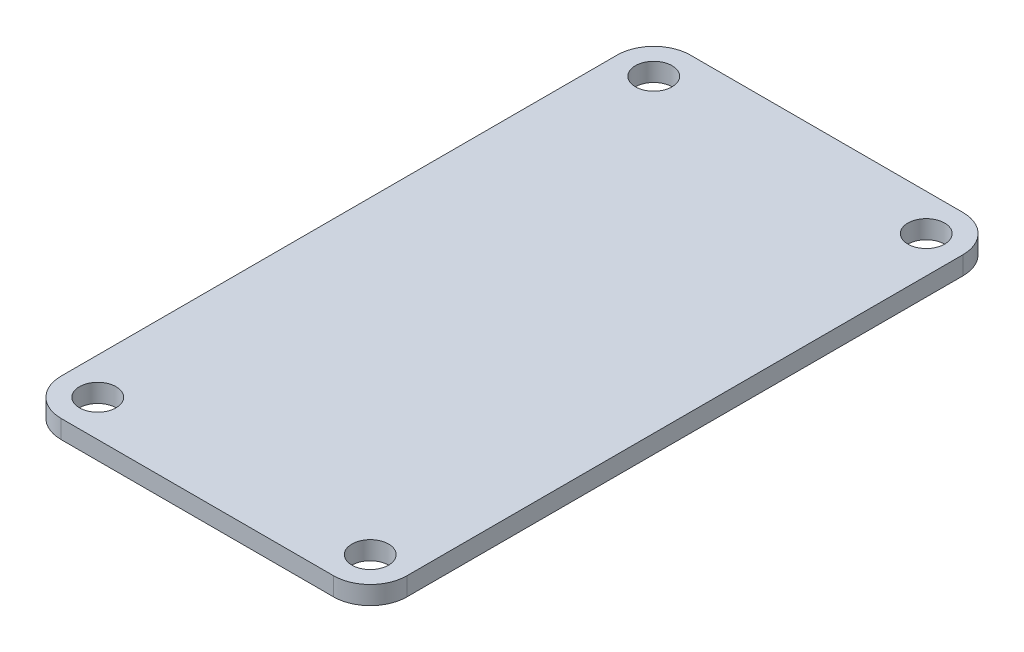
SolidWorks part; units mm, degrees
ref_plane "前视基准面" through (0, 0, 0) normal (0, 0, 1) x (1, 0, 0)
ref_plane "上视基准面" through (0, 0, 0) normal (0, 1, 0) x (1, 0, 0)
ref_plane "右视基准面" through (0, 0, 0) normal (1, 0, 0) x (0, 0, -1)
sketch "Sketch1" plane through (0, 0, 0) normal (0, 1, 0) x (1, 0, 0)
  line L1 (-11.15, 25.75) -> (11.15, 25.75)
  line L2 (-14.15, 22.75) -> (-14.15, -22.75)
  line L3 (-11.15, -25.75) -> (11.15, -25.75)
  line L4 (14.15, 22.75) -> (14.15, -22.75)
  line L5 (-14.15, 25.75) -> (14.15, -25.75) construction
  line L6 (-14.15, -25.75) -> (14.15, 25.75) construction
  arc A0 (-11.15, 25.75) -> (-14.15, 22.75) centre (-11.15, 22.75) ccw
  arc A1 (11.15, 25.75) -> (14.15, 22.75) centre (11.15, 22.75) cw
  arc A2 (11.15, -25.75) -> (14.15, -22.75) centre (11.15, -22.75) ccw
  arc A3 (-14.15, -22.75) -> (-11.15, -25.75) centre (-11.15, -22.75) ccw
  point P0 (0, 0)
  dimension "D3" = 3
  dimension "D1" = 51.5
  dimension "D2" = 28.3
extrude "Boss-Extrude1" add sketch "Sketch1" along normal mid plane 1.5
sketch "Sketch3" plane through (0, 0.75, 0) normal (0, 1, 0) x (1, 0, 0)
  circle A0 centre (-11.15, -22.75) radius 1.5
  circle A1 centre (-11.15, 22.75) radius 1.5
  circle A2 centre (11.15, -22.75) radius 1.5
  circle A3 centre (11.15, 22.75) radius 1.5
extrude "Cut-Extrude1" cut sketch "Sketch3" against normal up to next
